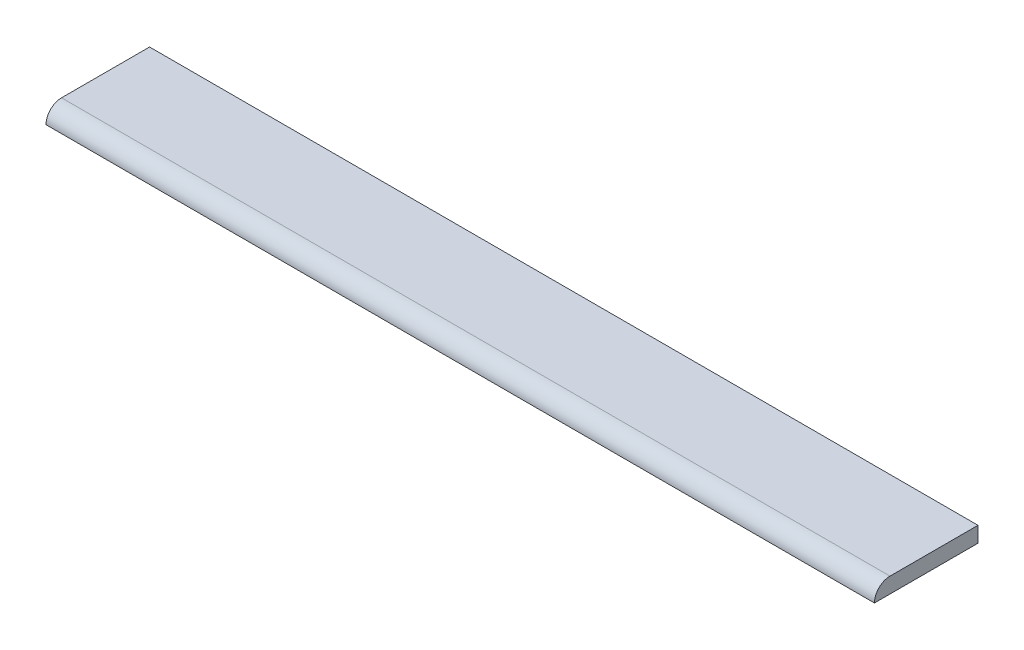
SolidWorks part; units mm, degrees
ref_plane "Plano frontal" through (0, 0, 0) normal (0, 0, 1) x (1, 0, 0)
ref_plane "Plano superior" through (0, 0, 0) normal (0, 1, 0) x (1, 0, 0)
ref_plane "Plano direito" through (0, 0, 0) normal (1, 0, 0) x (0, 0, -1)
sketch "Esboço1" plane through (0, 0, 0) normal (0, 1, 0) x (1, 0, 0)
  line L1 (-38.2642, 6.9626) -> (121.7358, 6.9626)
  line L2 (-38.2642, 6.9626) -> (-38.2642, -13.0374)
  line L3 (-38.2642, -13.0374) -> (121.7358, -13.0374)
  line L4 (121.7358, 6.9626) -> (121.7358, -13.0374)
extrude "Ressalto-extrusão1" add sketch "Esboço1" along normal blind 3
fillet "Filete2" radius 3 1 edges at (41.7358, 3, 13.0374)
